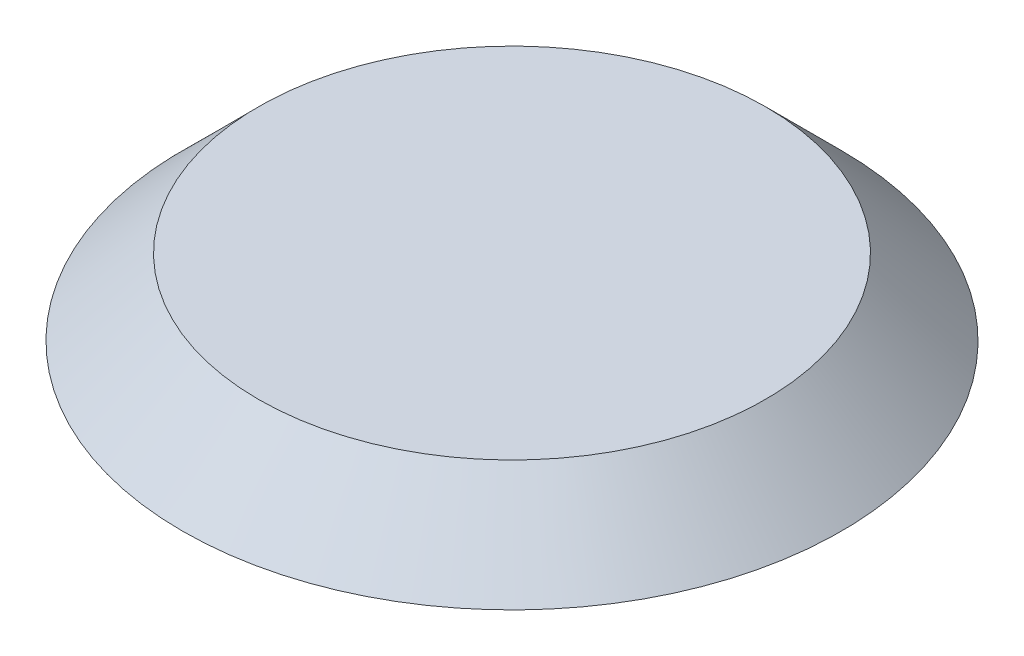
SolidWorks part; units mm, degrees
ref_plane "Plan de face" through (0, 0, 0) normal (0, 0, 1) x (1, 0, 0)
ref_plane "Plan de dessus" through (0, 0, 0) normal (0, 1, 0) x (1, 0, 0)
ref_plane "Plan de droite" through (0, 0, 0) normal (1, 0, 0) x (0, 0, -1)
sketch "Esquisse1" plane through (0, 0, 0) normal (0, 1, 0) x (1, 0, 0)
  circle A0 centre (0, 0) radius 13
extrude "Boss.-Extru.3" add sketch "Esquisse1" along normal blind 3
chamfer "Chanfrein2" distance 3 angle 45 1 edges at (0, 3, 13)
sketch "Esquisse3" plane through (0, 3, 0) normal (0, 1, 0) x (1, 0, 0)
  circle A0 centre (0, 0) radius 10 construction
  circle A1 centre (0, 0) radius 10
